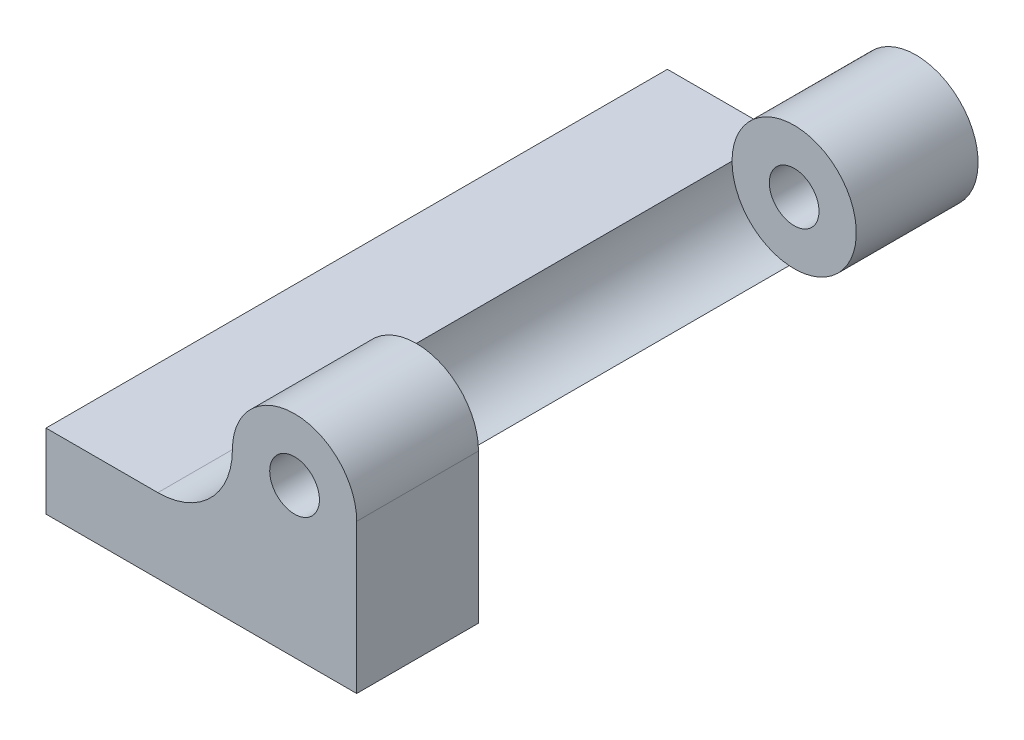
SolidWorks part; units mm, degrees
ref_plane "Front Plane" through (0, 0, 0) normal (0, 0, 1) x (1, 0, 0)
ref_plane "Top Plane" through (0, 0, 0) normal (0, 1, 0) x (1, 0, 0)
ref_plane "Right Plane" through (0, 0, 0) normal (1, 0, 0) x (0, 0, -1)
sketch "Sketch1" plane through (0, 0, 0) normal (0, 0, 1) x (1, 0, 0)
  line L0 (3, -1.5) -> (7, -1.5) construction
  line L1 (-3, -1.5) -> (3, -1.5)
  line L2 (-3, -1.5) -> (-3, 1.5)
  line L3 (-3, 1.5) -> (1.5, 1.5)
  line L7 (7, -1.5) -> (7, 4.5) construction
  arc A0 (6.8003, 2.008) -> (4.5, 4.5) centre (7, 4.5) ccw
  arc A1 (4.5, 4.5) -> (1.5, 1.5) centre (1.5, 4.5) cw
  arc A2 (6.8003, 2.008) -> (3, -1.5) centre (6.5192, -1.5) ccw
  circle A3 centre (7, 4.5) radius 1
  point P0 (0, 0)
  dimension "D3" = 5
  dimension "D6" = 2
  dimension "D1" = 3
  dimension "D2" = 6
  dimension "D4" = 4
  dimension "D5" = 6
extrude "Boss-Extrude1" add sketch "Sketch1" along normal blind 25
sketch "Sketch2" plane through (0, 0, 25) normal (0, 0, 1) x (1, 0, 0)
  circle A0 centre (7, 4.5) radius 2.5
extrude "Cut-Extrude1" cut sketch "Sketch2" along normal offset from surface 4.9 and the other way offset from surface 4.9 from offset 12.5 up to face at (2.1401, 1.6101, 25) other way up to face at (2.1401, 1.6101, 0) offset against normal yes
sketch "Sketch4" plane through (0, 0, 25) normal (0, 0, 1) x (1, 0, 0)
  line L0 (3, -1.5) -> (9.5, -1.5)
  line L1 (9.5, -1.5) -> (9.5, 4.5)
  arc A0 (6.8003, 2.008) -> (4.5, 4.5) centre (7, 4.5) ccw construction
  arc A1 (3, -1.5) -> (6.8003, 2.008) centre (6.5192, -1.5) cw
  arc A2 (6.8003, 2.008) -> (3, -1.5) centre (6.5192, -1.5) ccw construction
  arc A3 (6.8003, 2.008) -> (9.5, 4.5) centre (7, 4.5) ccw
extrude "Boss-Extrude2" add sketch "Sketch4" against normal blind 4.9
